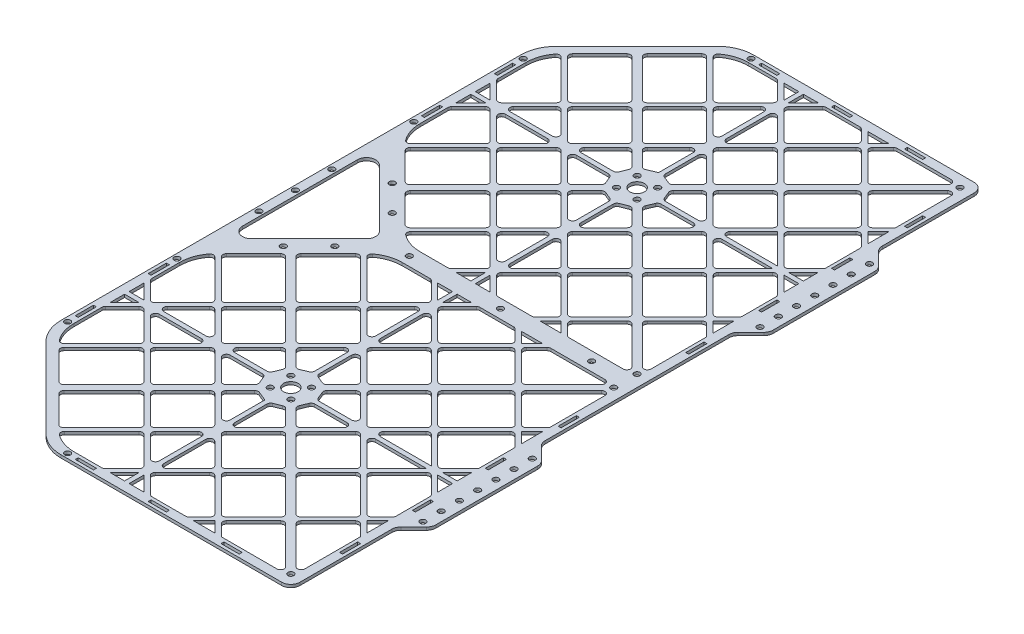
SolidWorks part; units mm, degrees
ref_plane "Front Plane" through (0, 0, 0) normal (0, 0, 1) x (1, 0, 0)
ref_plane "Top Plane" through (0, 0, 0) normal (0, 1, 0) x (1, 0, 0)
ref_plane "Right Plane" through (0, 0, 0) normal (1, 0, 0) x (0, 0, -1)
sketch "Sketch1" plane through (0, 0, 0) normal (0, 1, 0) x (1, 0, 0)
  line L0 (0, 190) -> (190, 0) construction
  line L1 (0, 0) -> (190, 0)
  line L2 (0, 0) -> (0, 190)
  line L3 (0, 190) -> (190, 190)
  line L4 (190, 0) -> (190, 190)
  line L5 (0, 95) -> (190, 95) construction
  circle A0 centre (95, 95) radius 90 construction
  circle A1 centre (95, 95) radius 8 construction
  circle A6 centre (95, 95) radius 13.5 construction
  circle A7 centre (89.3431, 100.6569) radius 1.6 construction
  circle A8 centre (100.6569, 100.6569) radius 1.6 construction
  circle A9 centre (100.6569, 89.3431) radius 1.6 construction
  circle A10 centre (89.3431, 89.3431) radius 1.6 construction
  point P8 (89.3431, 100.6569)
  point P19 (95, 95)
  point P22 (95, 95)
  dimension "D2" = 180
  dimension "D3" = 16
  dimension "D4" = 3.2
  dimension "D6" = 27
  dimension "D1" = 190
  dimension "D5" = 4
extrude "Boss-Extrude1" add sketch "Sketch1" along normal blind 1.6
sketch "Sketch2" plane through (0, 1.6, 0) normal (0, 1, 0) x (1, 0, 0)
  line L0 (0, 55.6497) -> (55.6497, 0)
  line L1 (0, 190) -> (0, 0) construction
  line L2 (0, 0) -> (190, 0) construction
  line L3 (95, 190) -> (95, 0) construction
  line L4 (190, 190) -> (0, 190) construction
  line L5 (0, 95) -> (190, 95) construction
  line L6 (0, 0) -> (0, 190) construction
  line L7 (190, 0) -> (190, 190) construction
  line L8 (0, 55.6497) -> (0, 0)
  line L9 (0, 0) -> (55.6497, 0)
  line L10 (27.8249, 27.8249) -> (31.3604, 31.3604) construction
  line L11 (0, 190) -> (48.5786, 190)
  line L12 (0, 141.4214) -> (0, 190)
  line L13 (0, 141.4214) -> (48.5786, 190)
  line L14 (0, 190) -> (190, 190) construction
  line L15 (0, 190) -> (190, 0) construction
  line L16 (24.2893, 165.7107) -> (31.3604, 158.6396) construction
  circle A0 centre (95, 95) radius 90 construction
  circle A1 centre (95, 95) radius 90 construction
  point P10 (95, 95)
  point P21 (95, 5)
  point P29 (24.2893, 165.7107)
  dimension "D1" = 5
  dimension "D2" = 5
  dimension "D3" = 10
extrude "Cut-Extrude1" cut sketch "Sketch2" against normal through all
sketch "Sketch4" plane through (0, 1.6, 0) normal (0, 1, 0) x (1, 0, 0)
  line L0 (190, 190) -> (48.5786, 190) construction
  line L1 (190, 0) -> (190, 190) construction
  line L2 (55.6497, 0) -> (190, 0) construction
  line L4 (0, 141.4214) -> (0, 55.6497) construction
  line L5 (0, 141.4214) -> (48.5786, 190) construction
  line L6 (190, 190) -> (48.5786, 190) construction
  line L7 (190, 0) -> (190, 190)
  line L8 (55.6497, 0) -> (190, 0) construction
  line L9 (55.6497, 0) -> (0, 55.6497) construction
  line L10 (0, 141.4214) -> (0, 55.6497) construction
  line L11 (0, 141.4214) -> (48.5786, 190) construction
  line L12 (185, 185) -> (57.7208, 185)
  line L13 (5, 132.2792) -> (57.7208, 185)
  line L14 (5, 132.2792) -> (5, 57.7208)
  line L15 (57.7208, 5) -> (5, 57.7208)
  line L16 (57.7208, 5) -> (185, 5)
  line L17 (185, 5) -> (185, 185)
  dimension "D1" = 20
  dimension "D2" = 5
  dimension "D3" = 5
  dimension "D4" = 5
  dimension "D5" = 5
  dimension "D6" = 5
extrude "Cut-Extrude2" cut sketch "Sketch4" against normal through all contours L16 L17 L12 L13 L14 L15
fillet "Fillet1" radius 20 6 edges at (0, 0.8, -55.6497) (55.6497, 0.8, 0) (57.7208, 0.8, -5) (5, 0.8, -57.7208) (5, 0.8, -132.2792) (57.7208, 0.8, -185)
fillet "Fillet5" radius 5 1 edges at (190, 0.8, 0)
sketch "Sketch5" plane through (0, 1.6, 0) normal (0, 1, 0) x (1, 0, 0)
  line L0 (0, 190) -> (190, 0) construction
  line L1 (104.5671, 85.4329) -> (108.5299, 95)
  line L2 (108.5299, 95) -> (104.5671, 104.5671)
  line L3 (104.5671, 104.5671) -> (95, 108.5299)
  line L4 (95, 108.5299) -> (85.4329, 104.5671)
  line L5 (85.4329, 104.5671) -> (81.4701, 95)
  line L6 (81.4701, 95) -> (85.4329, 85.4329)
  line L7 (85.4329, 85.4329) -> (95, 81.4701)
  line L8 (95, 81.4701) -> (104.5671, 85.4329)
  circle A0 centre (95, 95) radius 12.5 construction
  dimension "D1" = 25
extrude "Boss-Extrude2" add sketch "Sketch5" against normal up to surface (1.6 mm away) separate body up to face at (63.3473, 0, -95)
sketch "Sketch7" plane through (0, 1.6, 0) normal (0, 1, 0) x (1, 0, 0)
  line L0 (29.9462, 157.2254) -> (92.1716, 95)
  line L1 (10.8579, 138.1371) -> (51.8629, 179.1421) construction
  line L2 (66.0051, 5) -> (185, 5) construction
  line L3 (182.1716, 5) -> (185, 5)
  line L4 (0, 190) -> (190, 0) construction
  line L5 (185, 5) -> (185, 7.8284)
  line L6 (185, 5) -> (185, 185) construction
  line L7 (185, 7.8284) -> (97.8284, 95)
  line L8 (32.7746, 160.0538) -> (29.9462, 157.2254)
  line L9 (0, 95) -> (190, 95) construction
  line L10 (0, 0) -> (0, 190) construction
  line L11 (190, 0) -> (190, 190) construction
  line L12 (32.7746, 29.9462) -> (29.9462, 32.7746)
  line L13 (185, 182.1716) -> (97.8284, 95)
  line L14 (185, 185) -> (185, 182.1716)
  line L15 (182.1716, 185) -> (185, 185)
  line L16 (29.9462, 32.7746) -> (92.1716, 95)
  line L17 (95, 97.8284) -> (182.1716, 185)
  line L18 (95, 97.8284) -> (32.7746, 160.0538)
  line L19 (95, 92.1716) -> (182.1716, 5)
  line L20 (95, 92.1716) -> (32.7746, 29.9462)
  point P13 (31.3604, 158.6396)
  dimension "D1" = 4
extrude "Boss-Extrude3" add sketch "Sketch7" against normal up to surface (1.6 mm away) up to face at (63.3473, 0, -95)
sketch "Sketch10" plane through (0, 1.6, 0) normal (0, 1, 0) x (1, 0, 0)
  line L0 (96.25, 185) -> (96.25, 96.25)
  line L1 (182.1716, 185) -> (66.0051, 185) construction
  line L2 (66.0051, 5) -> (182.1716, 5) construction
  line L3 (96.25, 5) -> (93.75, 5)
  line L4 (93.75, 5) -> (93.75, 93.75)
  line L5 (93.75, 185) -> (96.25, 185)
  line L6 (0, 190) -> (190, 0) construction
  line L7 (0, 190) -> (190, 0) construction
  line L8 (185, 96.25) -> (185, 93.75)
  line L9 (95, 190) -> (95, 0) construction
  line L10 (0, 190) -> (190, 190) construction
  line L11 (0, 0) -> (190, 0) construction
  line L12 (5, 96.25) -> (93.75, 96.25)
  line L13 (185, 93.75) -> (96.25, 93.75)
  line L14 (5, 93.75) -> (5, 96.25)
  line L15 (93.75, 93.75) -> (5, 93.75)
  line L16 (93.75, 96.25) -> (93.75, 185)
  line L17 (96.25, 96.25) -> (185, 96.25)
  line L18 (96.25, 93.75) -> (96.25, 5)
  point P18 (95, 185)
  point P23 (95, 95)
  dimension "D1" = 2.5
  dimension "D2" = 2
extrude "Boss-Extrude5" add sketch "Sketch10" against normal up to surface (1.6 mm away) up to face at (137.8642, 0, -95)
sketch "Sketch13" plane through (0, 1.6, 0) normal (0, 1, 0) x (1, 0, 0)
  line L0 (10.5007, 52.22) -> (53.2807, 95)
  line L1 (29.9462, 32.7746) -> (10.8579, 51.8629) construction
  line L2 (10.8579, 138.1371) -> (29.9462, 157.2254) construction
  line L3 (143.2807, 185) -> (146.8162, 185)
  line L4 (146.8162, 185) -> (96.7678, 134.9515)
  line L5 (12.2685, 50.4523) -> (10.5007, 52.22)
  line L6 (32.7746, 160.0538) -> (51.8629, 179.1421) construction
  line L7 (182.1716, 185) -> (96.25, 185) construction
  line L8 (84.6045, 87.4329) -> (29.9462, 32.7746) construction
  line L9 (27.8249, 27.8249) -> (190, 190) construction
  line L10 (49.7918, 5.8579) -> (5.8579, 49.7918) construction
  line L11 (185, 143.2807) -> (185, 146.8162)
  line L12 (52.22, 10.5007) -> (95, 53.2807)
  line L13 (185, 146.8162) -> (134.9515, 96.7678)
  line L14 (50.4523, 12.2685) -> (52.22, 10.5007)
  line L15 (0, 95) -> (190, 95) construction
  line L16 (0, 95) -> (190, 95) construction
  line L17 (185, 46.7193) -> (185, 43.1838)
  line L18 (143.2807, 5) -> (146.8162, 5)
  line L19 (146.8162, 5) -> (96.7678, 55.0485)
  line L20 (10.5007, 137.78) -> (53.2807, 95)
  line L21 (52.22, 179.4993) -> (95, 136.7193)
  line L22 (185, 43.1838) -> (134.9515, 93.2322)
  line L23 (50.4523, 177.7315) -> (52.22, 179.4993)
  line L24 (12.2685, 139.5477) -> (10.5007, 137.78)
  line L25 (55.0485, 96.7678) -> (93.2322, 134.9515)
  line L26 (55.0485, 96.7678) -> (12.2685, 139.5477)
  line L27 (55.0485, 93.2322) -> (93.2322, 55.0485)
  line L28 (55.0485, 93.2322) -> (12.2685, 50.4523)
  line L29 (93.2322, 55.0485) -> (50.4523, 12.2685)
  line L30 (95, 53.2807) -> (143.2807, 5)
  line L31 (95, 56.8162) -> (56.8162, 95)
  line L32 (96.7678, 55.0485) -> (134.9515, 93.2322)
  line L33 (133.1838, 95) -> (95, 56.8162)
  line L34 (136.7193, 95) -> (185, 46.7193)
  line L35 (133.1838, 95) -> (95, 133.1838)
  line L36 (136.7193, 95) -> (185, 143.2807)
  line L37 (95, 136.7193) -> (143.2807, 185)
  line L38 (96.7678, 134.9515) -> (134.9515, 96.7678)
  line L39 (93.2322, 134.9515) -> (50.4523, 177.7315)
  line L40 (95, 133.1838) -> (56.8162, 95)
  dimension "D1" = 2.5
  dimension "D2" = 25
extrude "Boss-Extrude7" add sketch "Sketch13" against normal up to surface (1.6 mm away) up to face at (70.8321, 0, -154.0017)
sketch "Sketch14" plane through (0, 1.6, 0) normal (0, 1, 0) x (1, 0, 0)
  line L0 (5, 82.0746) -> (16.1576, 93.2322)
  line L1 (5, 93.75) -> (5, 66.0051) construction
  line L2 (143.2807, 185) -> (96.25, 185) construction
  line L3 (107.9254, 185) -> (104.3898, 185)
  line L4 (104.3898, 185) -> (95, 175.6102)
  line L5 (5, 85.6102) -> (5, 82.0746)
  line L6 (52.0307, 93.75) -> (10.5052, 52.2245) construction
  line L8 (0, 95) -> (190, 95) construction
  line L9 (85.6102, 185) -> (82.0746, 185)
  line L10 (185, 85.6102) -> (175.6102, 95)
  line L11 (82.0746, 185) -> (93.2322, 173.8424)
  line L12 (185, 82.0746) -> (185, 85.6102)
  line L13 (185, 104.3898) -> (185, 107.9254)
  line L14 (85.6102, 5) -> (95, 14.3898)
  line L15 (185, 107.9254) -> (173.8424, 96.7678)
  line L16 (82.0746, 5) -> (85.6102, 5)
  line L17 (104.3898, 5) -> (107.9254, 5)
  line L18 (5, 104.3898) -> (14.3898, 95)
  line L19 (107.9254, 5) -> (96.7678, 16.1576)
  line L20 (5, 107.9254) -> (5, 104.3898)
  line L21 (185, 96.25) -> (185, 143.2807) construction
  line L22 (93.2322, 173.8424) -> (16.1576, 96.7678)
  line L23 (95, 175.6102) -> (85.6102, 185)
  line L24 (96.7678, 173.8424) -> (107.9254, 185)
  line L25 (95, 172.0746) -> (172.0746, 95)
  line L26 (172.0746, 95) -> (95, 17.9254)
  line L27 (173.8424, 96.7678) -> (96.7678, 173.8424)
  line L28 (173.8424, 93.2322) -> (185, 82.0746)
  line L29 (175.6102, 95) -> (185, 104.3898)
  line L30 (95, 14.3898) -> (104.3898, 5)
  line L31 (96.7678, 16.1576) -> (173.8424, 93.2322)
  line L32 (93.2322, 16.1576) -> (82.0746, 5)
  line L33 (95, 17.9254) -> (17.9254, 95)
  line L34 (14.3898, 95) -> (5, 85.6102)
  line L35 (16.1576, 93.2322) -> (93.2322, 16.1576)
  line L36 (17.9254, 95) -> (95, 172.0746)
  line L37 (16.1576, 96.7678) -> (5, 107.9254)
  point P6 (95, 95)
  point P28 (95, 95)
  dimension "D1" = 2.5
  dimension "D2" = 25
  dimension "D3" = 4
extrude "Boss-Extrude8" add sketch "Sketch14" against normal up to surface (1.6 mm away) up to face at (42.4973, 0, -63.0034)
sketch "Sketch15" plane through (0, 1.6, 0) normal (0, 1, 0) x (1, 0, 0)
  line L0 (128.0366, 185) -> (185, 128.0366)
  line L1 (143.2807, 185) -> (107.9254, 185) construction
  line L2 (185, 107.9254) -> (185, 143.2807) construction
  line L3 (185, 128.0366) -> (185, 131.5721)
  line L4 (185, 146.8162) -> (185, 182.1716) construction
  line L5 (185, 131.5721) -> (131.5721, 185)
  line L6 (182.1716, 185) -> (146.8162, 185) construction
  line L7 (131.5721, 185) -> (128.0366, 185)
  line L8 (133.8909, 136.7193) -> (116.2132, 154.397) construction
  line L9 (0, 95) -> (190, 95) construction
  line L10 (0, 95) -> (190, 95) construction
  line L11 (131.5721, 5) -> (128.0366, 5)
  line L12 (185, 58.4279) -> (131.5721, 5)
  line L13 (185, 61.9634) -> (185, 58.4279)
  line L14 (128.0366, 5) -> (185, 61.9634)
  dimension "D1" = 2.5
  dimension "D2" = 30
extrude "Boss-Extrude9" add sketch "Sketch15" against normal up to surface (1.6 mm away) up to face at (7.7133, 0, -98.9633)
fillet "Fillet3" radius 2 32 edges at (77.3223, 0.8, -154.397) (135.6586, 0.8, -177.3779) (175.6102, 0.8, -137.4264) (156.1647, 0.8, -114.4454) (117.2739, 0.8, -75.5546) (139.1942, 0.8, -12.6221) (93.2322, 0.8, -16.1576) (81.9879, 0.8, -96.25) (115.5061, 0.8, -77.3223) (108.0121, 0.8, -96.25) (102.5671, 0.8, -84.6045) (96.25, 0.8, -19.1754) (10.5052, 0.8, -52.2245) (146.8162, 0.8, -5) (93.75, 0.8, -137.9693) (75.5546, 0.8, -156.1647) (75.5546, 0.8, -117.2739) (16.1576, 0.8, -96.7678) (5, 0.8, -107.9254) (96.7678, 0.8, -55.0485) (10.5052, 0.8, -137.7755) (75.5546, 0.8, -33.8353) (114.4454, 0.8, -33.8353) (156.8718, 0.8, -30.2997) (177.3779, 0.8, -50.8058) (115.5061, 0.8, -112.6777) (114.4454, 0.8, -152.6292) (96.25, 0.8, -170.8246) (82.0746, 0.8, -185) (58.0662, 0.8, -96.25) (131.9338, 0.8, -93.75) (74.4939, 0.8, -77.3223)
sketch "Sketch6" plane through (0, 1.6, 0) normal (0, 1, 0) x (1, 0, 0)
  circle A0 centre (89.3431, 89.3431) radius 1.6 construction
  circle A1 centre (100.6569, 89.3431) radius 1.6 construction
  circle A2 centre (100.6569, 100.6569) radius 1.6 construction
  circle A3 centre (89.3431, 100.6569) radius 1.6 construction
  circle A4 centre (89.3431, 89.3431) radius 1.6
  circle A5 centre (100.6569, 89.3431) radius 1.6
  circle A6 centre (100.6569, 100.6569) radius 1.6
  circle A7 centre (89.3431, 100.6569) radius 1.6
  circle A8 centre (95, 95) radius 4
  dimension "D1" = 8
extrude "Cut-Extrude3" cut sketch "Sketch6" against normal through all
sketch "Sketch11" plane through (0, 1.6, 0) normal (0, 1, 0) x (1, 0, 0)
  line L0 (190, 2.5) -> (180.6767, 2.5) construction
  line L5 (190, 0) -> (190, 190) construction
  line L6 (180.6767, 5) -> (180.6767, 0) construction
  line L7 (96.25, 5) -> (104.3898, 5) construction
  line L8 (0, 0) -> (190, 0) construction
  line L9 (110, 3.305) -> (120, 3.305)
  line L10 (150, 3.305) -> (160, 3.305)
  line L11 (150, 3.305) -> (150, 1.695)
  line L12 (150, 1.695) -> (160, 1.695)
  line L13 (160, 3.305) -> (160, 1.695)
  line L14 (150, 3.305) -> (160, 1.695) construction
  line L15 (150, 1.695) -> (160, 3.305) construction
  line L16 (110, 1.695) -> (120, 1.695)
  line L17 (110, 3.305) -> (110, 1.695)
  line L18 (120, 3.305) -> (120, 1.695)
  line L19 (70, 3.305) -> (80, 3.305)
  line L20 (70, 1.695) -> (80, 1.695)
  line L21 (70, 3.305) -> (70, 1.695)
  line L22 (80, 3.305) -> (80, 1.695)
  line L27 (0, 95) -> (190, 95) construction
  line L28 (0, 95) -> (190, 95) construction
  line L43 (185, 178.815) -> (190, 178.815) construction
  line L44 (185, 96.25) -> (185, 104.3898) construction
  line L45 (187.5, 190) -> (187.5, 178.815) construction
  line L46 (0, 190) -> (190, 190) construction
  line L47 (186.695, 120) -> (188.305, 120)
  line L48 (186.695, 160) -> (188.305, 160)
  line L49 (186.695, 160) -> (186.695, 150)
  line L50 (186.695, 150) -> (188.305, 150)
  line L51 (188.305, 160) -> (188.305, 150)
  line L52 (186.695, 160) -> (188.305, 150) construction
  line L53 (186.695, 150) -> (188.305, 160) construction
  line L54 (186.695, 120) -> (186.695, 110)
  line L55 (188.305, 120) -> (188.305, 110)
  line L56 (186.695, 110) -> (188.305, 110)
  line L57 (186.695, 80) -> (188.305, 80)
  line L58 (186.695, 80) -> (186.695, 70)
  line L59 (188.305, 80) -> (188.305, 70)
  line L60 (186.695, 70) -> (188.305, 70)
  line L61 (186.695, 40) -> (188.305, 40)
  line L62 (186.695, 40) -> (186.695, 30)
  line L63 (188.305, 40) -> (188.305, 30)
  line L64 (186.695, 30) -> (188.305, 30)
  line L65 (95, 0) -> (95, 190) construction
  line L66 (3.305, 70) -> (1.695, 70)
  line L67 (1.695, 80) -> (1.695, 70)
  line L68 (3.305, 80) -> (3.305, 70)
  line L69 (3.305, 80) -> (1.695, 80)
  line L70 (3.305, 110) -> (1.695, 110)
  line L71 (1.695, 120) -> (1.695, 110)
  line L72 (3.305, 120) -> (3.305, 110)
  line L73 (3.305, 120) -> (1.695, 120)
  point P10 (180.6767, 2.5)
  point P11 (155, 2.5)
  point P49 (187.5, 178.815)
  point P52 (187.5, 155)
  dimension "D1" = 1.61
  dimension "D2" = 10
  dimension "D3" = 30
  dimension "D5" = 30
  dimension "D6" = 30
  dimension "D8" = 30
  dimension "D4" = 3
  dimension "D7" = 4
extrude "Cut-Extrude5" cut sketch "Sketch11" against normal through all
sketch "Sketch18" plane through (0, 1.6, 0) normal (0, 1, 0) x (1, 0, 0)
  line L0 (190, 137.5) -> (190, 57.5)
  line L1 (190, 5) -> (190, 190) construction
  line L2 (190, 57.5) -> (200, 67.5)
  line L3 (200, 67.5) -> (200, 127.5)
  line L4 (200, 127.5) -> (190, 137.5)
  line L5 (49.7918, 5.8579) -> (5.8579, 49.7918) construction
  point P7 (190, 97.5)
  point P11 (190, 97.5)
  dimension "D1" = 10
  dimension "D2" = 80
extrude "Boss-Extrude11" add sketch "Sketch18" against normal up to surface (1.6 mm away) up to face at (115, 0, -2.5)
sketch "Sketch19" plane through (0, 1.6, 0) normal (0, 1, 0) x (1, 0, 0)
  line L0 (195, 132.5) -> (195, 62.5) construction
  line L1 (200, 67.5) -> (200, 127.5) construction
  line L2 (190, 137.5) -> (190, 57.5) construction
  line L3 (190, 97.5) -> (200, 97.5) construction
  line L4 (200, 127.5) -> (190, 137.5) construction
  circle A2 centre (195, 97.5) radius 1.6
  circle A3 centre (195, 107.5) radius 1.6
  circle A4 centre (195, 117.5) radius 1.6
  circle A5 centre (195, 127.5) radius 1.6
  circle A6 centre (195, 87.5) radius 1.6
  circle A7 centre (195, 77.5) radius 1.6
  circle A8 centre (195, 67.5) radius 1.6
  point P3 (195, 87.5)
  point P4 (195, 97.5)
  point P5 (200, 97.5)
  point P6 (190, 97.5)
  point P15 (195, 107.5)
  point P16 (195, 97.5)
  point P23 (195, 117.5)
  point P26 (195, 127.5)
  point P31 (195, 77.5)
  point P34 (195, 67.5)
  dimension "D1" = 3.2
  dimension "D2" = 4
  dimension "D4" = 10
  dimension "D5" = 10
  dimension "D3" = 4
extrude "Cut-Extrude8" cut sketch "Sketch19" against normal through all
fillet "Fillet4" radius 5 4 edges at (200, 0.8, -127.5) (190, 0.8, -137.5) (190, 0.8, -57.5) (200, 0.8, -67.5)
sketch "Sketch17" plane through (0, 1.6, 0) normal (0, 1, 0) x (1, 0, 0)
  line L0 (36.662, 39.4904) -> (39.4904, 36.662) construction
  line L1 (35.603, 96.25) -> (35.603, 93.75) construction
  line L2 (47.2023, 96.25) -> (24.0038, 96.25) construction
  line L3 (51.8665, 54.6949) -> (31.3604, 34.1888) construction
  line L4 (34.1888, 31.3604) -> (54.6949, 51.8665) construction
  line L5 (24.0038, 93.75) -> (47.2023, 93.75) construction
  line L6 (35.603, 95) -> (0, 95) construction
  line L7 (0, 141.4214) -> (0, 63.934) construction
  line L8 (24.2893, 165.7107) -> (188.5355, 1.4645) construction
  line L9 (0, 141.4214) -> (48.5786, 190) construction
  line L10 (158.2861, 28.8855) -> (178.7574, 8.4142) construction
  line L11 (70, 2.5) -> (110, 2.5) construction
  line L12 (70, 3.305) -> (70, 1.695) construction
  line L13 (110, 3.305) -> (110, 1.695) construction
  line L14 (27.8249, 27.8249) -> (38.0762, 38.0762) construction
  line L15 (49.7918, 5.8579) -> (5.8579, 49.7918) construction
  circle A0 centre (183.5858, 6.4142) radius 1.6
  arc A2 (185, 0) -> (190, 5) centre (185, 5) ccw construction
  circle A3 centre (65, 2.5) radius 1.6
  circle A5 centre (2.5, 65) radius 1.6
  circle A6 centre (2.5, 125) radius 1.6
  circle A7 centre (183.5858, 183.5858) radius 1.6
  dimension "D1" = 3.2
  dimension "D2" = 7
  dimension "D4" = 5
extrude "Cut-Extrude7" cut sketch "Sketch17" against normal through all and the other way through all
mirror "Mirror2" about plane through (0, 1.6, -190) normal (0, 0, 1) of bodies 128 118
sketch "Sketch12" plane through (0, 1.6, 0) normal (0, 1, 0) x (1, 0, 0)
  line L0 (0, 238.5786) -> (0, 141.4214)
  line L1 (0, 141.4214) -> (5, 141.4214)
  line L2 (5, 141.4214) -> (5, 238.5786)
  line L3 (5, 238.5786) -> (0, 238.5786)
  line L4 (5, 123.9949) -> (5, 108.7538) construction
extrude "Boss-Extrude6" add sketch "Sketch12" against normal up to surface (1.6 mm away) up to face at (183.5858, 0, -185.1858)
fillet "Fillet2" radius 5 3 edges at (5, 0.8, -146.4214) (5, 0.8, -233.5786) (48.5786, 0.8, -190)
sketch "Sketch16" plane through (0, 1.6, 0) normal (0, 1, 0) x (1, 0, 0)
  line L0 (71.7676, 195) -> (71.7676, 185) construction
  line L1 (81.2462, 195) -> (66.0051, 195) construction
  line L2 (81.2462, 185) -> (66.0051, 185) construction
  line L4 (190, 139.5711) -> (190, 240.4289) construction
  circle A0 centre (165, 190) radius 1.6
  circle A1 centre (115, 190) radius 1.6
  circle A2 centre (65, 190) radius 1.6
  point P8 (71.7676, 190)
  point P9 (75, 190)
  point P12 (115, 190)
  dimension "D3" = 50
  dimension "D4" = 3.2
  dimension "D1" = 25
  dimension "D2" = 3
extrude "Cut-Extrude6" cut sketch "Sketch16" against normal through all
sketch "Sketch20" plane through (0, 1.6, 0) normal (0, 1, 0) x (1, 0, 0)
  line L0 (2.5, 126.6) -> (2.5, 253.4) construction
  line L1 (2.5, 190) -> (190, 190) construction
  line L2 (190, 139.5711) -> (190, 240.4289) construction
  line L3 (29.2893, 209.2893) -> (36.3604, 216.3604) construction
  line L4 (13.5355, 225.0431) -> (45.0431, 193.5355) construction
  line L5 (34.1888, 218.532) -> (49.0381, 203.6827) construction
  line L6 (0, 245.6497) -> (55.6497, 190) construction
  line L7 (0, 316.066) -> (0, 63.934) construction
  circle A0 centre (2.5, 125) radius 1.6 construction
  circle A1 centre (2.5, 255) radius 1.6 construction
  circle A4 centre (39.8959, 205.7538) radius 1.6
  circle A5 centre (25.7538, 219.8959) radius 1.6
  circle A6 centre (25.7538, 160.1041) radius 1.6
  circle A7 centre (39.8959, 174.2462) radius 1.6
  circle A8 centre (2.5, 170) radius 1.6
  circle A9 centre (2.5, 190) radius 1.6
  circle A10 centre (2.5, 210) radius 1.6
  point P23 (32.8249, 212.8249)
  dimension "D2" = 10
  dimension "D3" = 3.2
  dimension "D1" = 126.8
  dimension "D4" = 20
extrude "Cut-Extrude9" cut sketch "Sketch20" against normal through all
